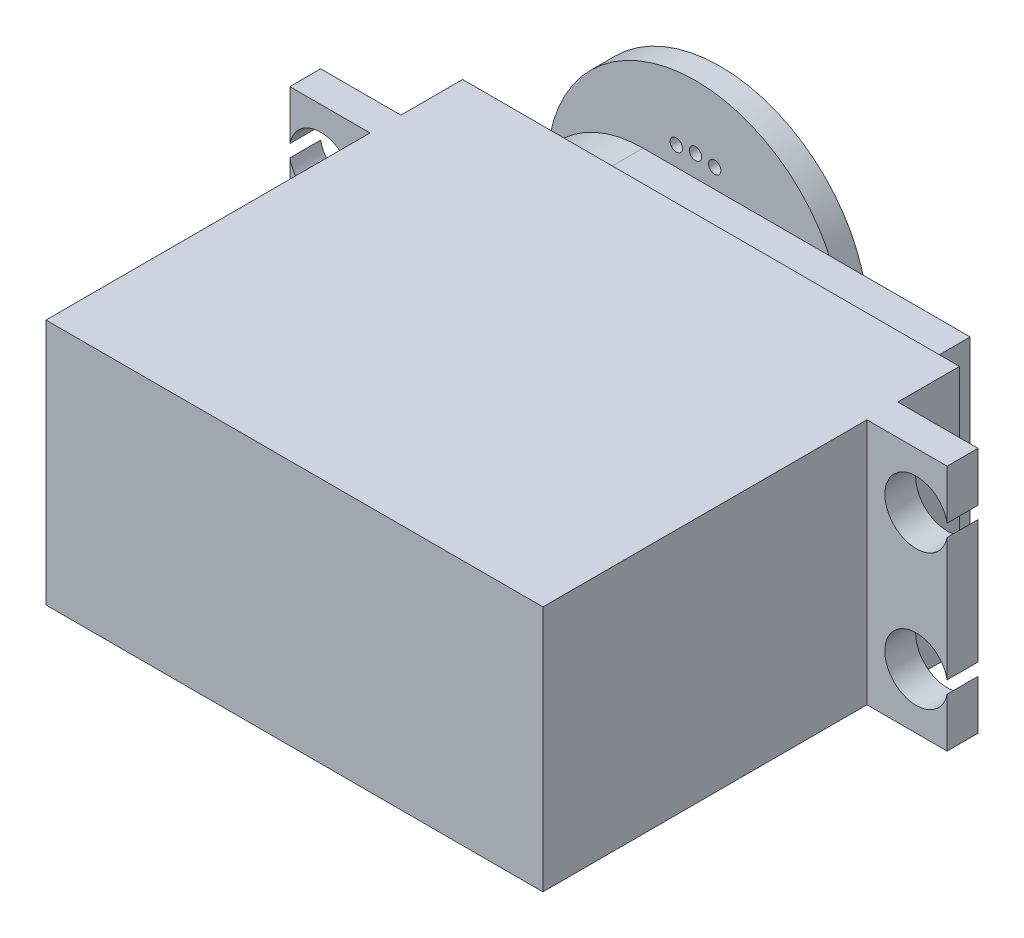
SolidWorks part; units mm, degrees
ref_plane "Front Plane" through (0, 0, 0) normal (0, 0, 1) x (1, 0, 0)
ref_plane "Top Plane" through (0, 0, 0) normal (0, 1, 0) x (1, 0, 0)
ref_plane "Right Plane" through (0, 0, 0) normal (1, 0, 0) x (0, 0, -1)
sketch "Sketch1" plane through (0, 0, 0) normal (0, 1, 0) x (1, 0, 0)
  line L0 (20.135, 9.38) -> (26.635, 9.38)
  line L1 (-20.135, -16.88) -> (20.135, -16.88)
  line L2 (20.135, -16.88) -> (20.135, 9.38)
  line L3 (-20.135, 16.88) -> (20.135, 16.88)
  line L4 (-20.135, 9.38) -> (-20.135, -16.88)
  line L5 (-20.135, -16.88) -> (20.135, 16.88) construction
  line L6 (-20.135, 16.88) -> (20.135, -16.88) construction
  line L7 (20.135, 11.88) -> (20.135, 16.88)
  line L8 (26.635, 9.38) -> (26.635, 11.88)
  line L9 (20.135, 11.88) -> (26.635, 11.88)
  line L10 (-20.135, 11.88) -> (-26.635, 11.88)
  line L11 (-20.135, 11.88) -> (-20.135, 16.88)
  line L12 (-26.635, 11.88) -> (-26.635, 9.38)
  line L13 (-20.135, 9.38) -> (-26.635, 9.38)
  point P0 (0, 0)
  dimension "D1" = 40.27
  dimension "D2" = 33.76
  dimension "D3" = 2.5
  dimension "D4" = 5
  dimension "D5" = 6.5
  dimension "D6" = 2.5
  dimension "D7" = 6.5
extrude "Boss-Extrude1" add sketch "Sketch1" along normal blind 20
sketch "Sketch3" plane through (0, 0, -16.88) normal (0, 0, -1) x (-1, 0, 0)
  line L0 (-20.135, 0) -> (20.135, 0) construction
  line L1 (18, 19.5) -> (-18, 19.5)
  line L2 (18, 19.5) -> (18, 0.5)
  line L3 (18, 0.5) -> (-18, 0.5)
  line L4 (-18, 19.5) -> (-18, 0.5)
  line L5 (18, 19.5) -> (-18, 0.5) construction
  line L6 (18, 0.5) -> (-18, 19.5) construction
  point P0 (0, 10)
  dimension "D1" = 10
  dimension "D2" = 19
  dimension "D3" = 36
extrude "Boss-Extrude2" add sketch "Sketch3" along normal blind 3
fillet "Fillet3" radius 9.5 1 edges at (-18, 19.5, -18.38) type face fillet first side face at (0, 19.5, -18.38) second side face at (-18, 10, -18.38)
fillet "Fillet4" radius 9.5 1 edges at (-18, 0.5, -18.38) type face fillet first side face at (-18, 5.25, -18.38) second side face at (0, 0.5, -18.38)
sketch "Sketch4" plane through (0, 0, -19.88) normal (0, 0, -1) x (-1, 0, 0)
  circle A0 centre (8.5, 10) radius 5
  dimension "D1" = 10
  dimension "D2" = 9.5
extrude "Boss-Extrude3" add sketch "Sketch4" along normal blind 4.24
sketch "Sketch5" plane through (0, 0, -24.12) normal (0, 0, -1) x (-1, 0, 0)
  circle A0 centre (8.5, 10.1285) radius 12
  dimension "D2" = 24
  dimension "D1" = 9.5
extrude "Boss-Extrude4" add sketch "Sketch5" along normal blind 2
sketch "Sketch6" plane through (0, 0, -11.88) normal (0, 0, -1) x (-1, 0, 0)
  line L0 (-26.635, 20) -> (-20.135, 20) construction
  line L1 (-26.635, 20) -> (-26.635, 0) construction
  line L2 (-26.635, 0) -> (-20.135, 0) construction
  line L3 (-24.135, 15.5) -> (24.135, 15.5) construction
  line L4 (-24.135, 4.5) -> (24.135, 4.5) construction
  line L6 (26.635, 20) -> (26.635, 0) construction
  circle A0 centre (-24.135, 15.5) radius 2.55
  circle A1 centre (-24.135, 4.5) radius 2.55
  circle A2 centre (24.135, 15.5) radius 2.55
  circle A3 centre (24.135, 4.5) radius 2.55
  point P8 (-23.385, 0)
  dimension "D1" = 5.1
  dimension "D4" = 5.1
  dimension "D2" = 4.5
  dimension "D3" = 2.5
  dimension "D5" = 4.5
  dimension "D6" = 2.5
  dimension "D8" = 48.27
  dimension "D10" = 48.27
  dimension "D7" = 2
  dimension "D9" = 2
extrude "Cut-Extrude4" cut sketch "Sketch6" against normal through all
sketch "Sketch8" plane through (0, 0, -26.12) normal (0, 0, -1) x (-1, 0, 0)
  circle A0 centre (8.5, 10) radius 0.5
  circle A1 centre (1.6755, 11.5576) radius 0.5
  circle A2 centre (1.5, 10) radius 0.5
  circle A7 centre (6.9424, 16.8245) radius 0.5
  circle A8 centre (8.5, 17) radius 0.5
  circle A9 centre (10.0576, 16.8245) radius 0.5
  circle A14 centre (15.3245, 11.5576) radius 0.5
  circle A15 centre (15.5, 10) radius 0.5
  circle A16 centre (15.3245, 8.4424) radius 0.5
  circle A21 centre (10.0576, 3.1755) radius 0.5
  circle A22 centre (8.5, 3) radius 0.5
  circle A23 centre (6.9424, 3.1755) radius 0.5
  circle A28 centre (1.6755, 8.4424) radius 0.5
  circle A29 centre (2.1932, 13.0372) radius 0.5 [skipped]
  circle A30 centre (3.0272, 14.3644) radius 0.5 [skipped]
  circle A31 centre (4.1356, 15.4728) radius 0.5 [skipped]
  circle A32 centre (5.4628, 16.3068) radius 0.5 [skipped]
  circle A33 centre (11.5372, 16.3068) radius 0.5 [skipped]
  circle A34 centre (12.8644, 15.4728) radius 0.5 [skipped]
  circle A35 centre (13.9728, 14.3644) radius 0.5 [skipped]
  circle A36 centre (14.8068, 13.0372) radius 0.5 [skipped]
  circle A37 centre (14.8068, 6.9628) radius 0.5 [skipped]
  circle A38 centre (13.9728, 5.6356) radius 0.5 [skipped]
  circle A39 centre (12.8644, 4.5272) radius 0.5 [skipped]
  circle A40 centre (11.5372, 3.6932) radius 0.5 [skipped]
  circle A41 centre (5.4628, 3.6932) radius 0.5 [skipped]
  circle A42 centre (4.1356, 4.5272) radius 0.5 [skipped]
  circle A43 centre (3.0272, 5.6356) radius 0.5 [skipped]
  circle A44 centre (2.1932, 6.9628) radius 0.5 [skipped]
  point P63 (8.5, 10)
  dimension "D1" = 9.5
  dimension "D3" = 1
  dimension "D5" = 1
  dimension "D2" = 9.5
  dimension "D4" = 7
  dimension "D6" = 28
extrude "Cut-Extrude5" cut sketch "Sketch8" against normal blind 2
